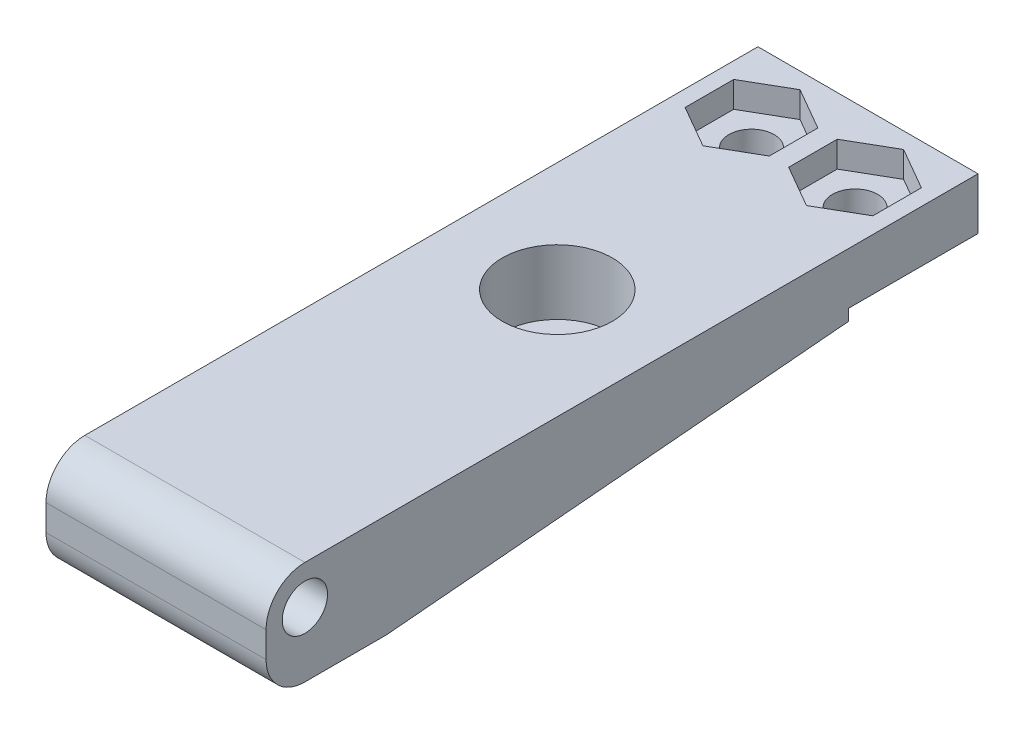
SolidWorks part; units mm, degrees
material "ABS"
ref_plane "Front Plane" through (0, 0, 0) normal (0, 0, 1) x (1, 0, 0)
ref_plane "Top Plane" through (0, 0, 0) normal (0, 1, 0) x (1, 0, 0)
ref_plane "Right Plane" through (0, 0, 0) normal (1, 0, 0) x (0, 0, -1)
sketch "Sketch1" plane through (0, 0, 0) normal (1, 0, 0) x (0, 0, -1)
  line L0 (-3, 0) -> (-3, -5.8119)
  line L4 (0, 3) -> (52, 3)
  line L5 (52, 3) -> (52, -1)
  line L6 (-3, -5.8119) -> (52, -1)
  line L7 (52, -1) -> (42, -1)
  line L8 (-3, 0) -> (0, 0) construction
  line L9 (42, -1) -> (42, -1.8749)
  line L10 (-3, -5) -> (6.2798, -5)
  circle A0 centre (0, 0) radius 1.75
  arc A1 (0, 3) -> (-3, 0) centre (0, 0) ccw
  dimension "D1" = 3.5
  dimension "D2" = 3
  dimension "D3" = 4
  dimension "D4" = 5
  dimension "D5" = 10
  dimension "D6" = 55
  dimension "D7" = 8
extrude "Boss-Extrude1" add sketch "Sketch1" along normal mid plane 17 contours L4 A1 A0 L0 L6 L9 L7 L5 region at (0, -0.3114, -21.7202)
fillet "Fillet1" radius 3 1 edges at (0, -5, 3)
sketch "Sketch2" plane through (0, 3, 0) normal (0, 1, 0) x (1, 0, 0)
  line L0 (-8.5, 47) -> (-4, 47) construction
  line L1 (-8.5, 0) -> (-8.5, 52) construction
  line L2 (-4, 47) -> (4, 47) construction
  line L3 (4, 47) -> (8.5, 47) construction
  line L4 (8.5, 0) -> (8.5, 52) construction
  line L5 (8.5, 52) -> (-8.5, 52) construction
  line L7 (0.75, 45.1236) -> (4, 43.2472)
  line L8 (4, 43.2472) -> (7.25, 45.1236)
  line L9 (7.25, 45.1236) -> (7.25, 48.8764)
  line L10 (7.25, 48.8764) -> (4, 50.7528)
  line L11 (4, 50.7528) -> (0.75, 48.8764)
  line L12 (0.75, 48.8764) -> (0.75, 45.1236)
  line L13 (-0.75, 48.8764) -> (-4, 50.7528)
  line L14 (-4, 50.7528) -> (-7.25, 48.8764)
  line L15 (-7.25, 48.8764) -> (-7.25, 45.1236)
  line L16 (-7.25, 45.1236) -> (-4, 43.2472)
  line L17 (-4, 43.2472) -> (-0.75, 45.1236)
  line L18 (-0.75, 45.1236) -> (-0.75, 48.8764)
  circle A0 centre (-4, 47) radius 1.75
  circle A1 centre (4, 47) radius 1.75
  circle A2 centre (4, 47) radius 3.25 construction
  circle A3 centre (-4, 47) radius 3.25 construction
  dimension "D1" = 3.5
  dimension "D2" = 8
  dimension "7.5" = 5
  dimension "D4" = 6.5
extrude "Cut-Extrude1" cut sketch "Sketch2" against normal through all contours A0 | A1 region at (-4, 3, -47) region at (4, 3, -47)
extrude "Cut-Extrude2" cut sketch "Sketch2<3>" against normal blind 2 contours L11 L12 L7 L8 L9 L10 A1 | L17 L18 L13 L14 L15 L16 A0 region at (0.8493, 3, -47) region at (-0.8493, 3, -47)
sketch "Sketch2<3>" plane through (0, 3, 0) normal (0, 1, 0) x (1, 0, 0) same geometry as "Sketch2"
sketch "Sketch3" plane through (0, 3, 0) normal (0, 1, 0) x (1, 0, 0)
  line L0 (0, 28) -> (0, 0) construction
  line L1 (0, 28) -> (0, 38) construction
  circle A0 centre (0, 28) radius 4.25
  dimension "D3" = 8.5
  dimension "D1" = 38
  dimension "D2" = 10
extrude "Cut-Extrude3" cut sketch "Sketch3" against normal blind 5
